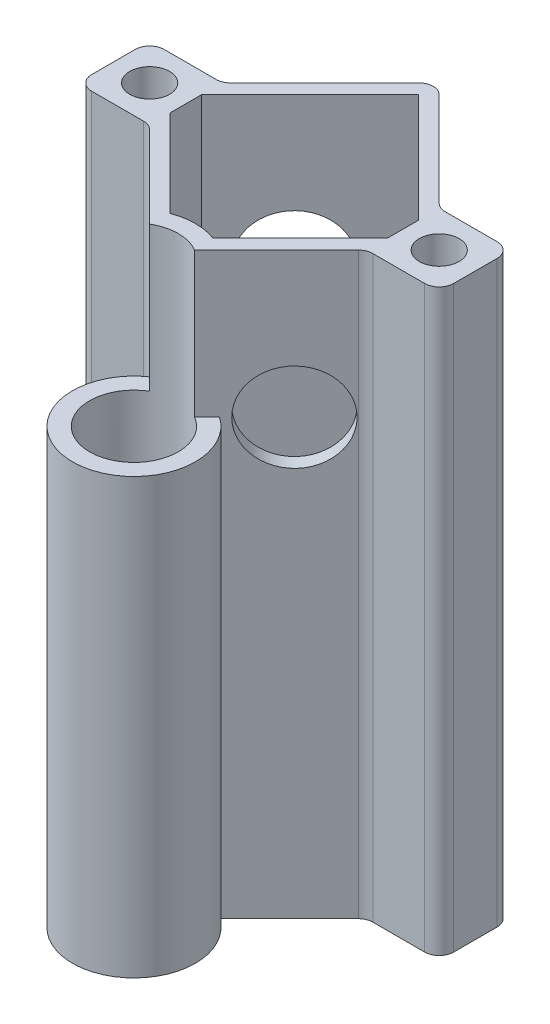
SolidWorks part; units mm, degrees
ref_plane "Front Plane" through (0, 0, 0) normal (0, 0, 1) x (1, 0, 0)
ref_plane "Top Plane" through (0, 0, 0) normal (0, 1, 0) x (1, 0, 0)
ref_plane "Right Plane" through (0, 0, 0) normal (1, 0, 0) x (0, 0, -1)
sketch "Sketch2" plane through (0, 0, 0) normal (0, 1, 0) x (1, 0, 0)
  line L32 (-25.4, 0) -> (-19.05, 0) construction
  line L33 (-25.4, 0) -> (0, 25.4)
  line L34 (-19.05, -6.35) -> (-31.75, -6.35)
  line L35 (-19.05, -6.35) -> (-19.05, 6.35)
  line L36 (-19.05, 6.35) -> (-31.75, 6.35)
  line L37 (-31.75, -6.35) -> (-31.75, 6.35)
  line L38 (-19.05, -6.35) -> (-31.75, 6.35) construction
  line L39 (-19.05, 6.35) -> (-31.75, -6.35) construction
  line L40 (19.05, -6.35) -> (31.75, -6.35)
  line L41 (19.05, -6.35) -> (19.05, 6.35)
  line L42 (19.05, 6.35) -> (31.75, 6.35)
  line L43 (31.75, -6.35) -> (31.75, 6.35)
  line L44 (19.05, -6.35) -> (31.75, 6.35) construction
  line L45 (19.05, 6.35) -> (31.75, -6.35) construction
  line L46 (0, -55) -> (0, 55) construction
  line L47 (0, 25.4) -> (25.4, 0)
  line L48 (25.4, 0) -> (0, -25.4)
  line L49 (0, -25.4) -> (-25.4, 0)
  line L50 (-19.05, 2.7579) -> (0, 21.8079)
  line L51 (19.05, 0) -> (25.4, 0) construction
  line L52 (0, 21.8079) -> (19.05, 2.7579)
  line L53 (19.05, -2.7579) -> (0, -21.8079)
  line L54 (0, -21.8079) -> (-19.05, -2.7579)
  line L55 (-21.8079, 0) -> (0, 21.8079) construction
  line L56 (0, -21.8079) -> (-21.8079, 0) construction
  line L57 (0, 21.8079) -> (21.8079, 0) construction
  line L58 (21.8079, 0) -> (0, -21.8079) construction
  circle A0 centre (25.4, 0) radius 3.4925
  circle A1 centre (-25.4, 0) radius 3.4925
  point P0 (0, 0)
  point P5 (0, 0)
  dimension "D1" = 50.8
  dimension "D2" = 6.35
  dimension "D4" = 6.985
  dimension "D3" = 2.54
  dimension "D5" = 50.8
  dimension "D6" = 12.7
extrude "Boss-Extrude1" add sketch "Sketch2" along normal blind 101.6 contours L42 L36 | L40 L34 | L50 L52 L41 L47 L33 L35 | A1 L49 L35 L33 | A1 L33 L36 L37 L34 L49 | L53 L54 L35 L49 L48 L41 | A0 L47 L41 L48 | A0 L48 L40 L43 L42 L47 region at (-20.5007, 0, 0) region at (-9.2116, 0, -15.5616) region at (-21.1172, 0, -4.5368) region at (20.5007, 0, 0) region at (25.4, 0, -6.1704) region at (-9.8384, 0, 12.5963)
fillet "Fillet1" radius 2.54 10 edges at (-31.75, 50.8, -6.35) (-31.75, 50.8, 6.35) (31.75, 50.8, 6.35) (31.75, 50.8, -6.35) (-19.05, 50.8, 6.35) (0, 50.8, 25.4) (19.05, 50.8, 6.35) (19.05, 50.8, -6.35) (0, 50.8, -25.4) (-19.05, 50.8, -6.35)
ref_axis "Axis2" through (0, -5.08, 0) along (0, 1, 0)
sketch "Sketch12" plane through (-12.7, 0, -12.7) normal (-0.7071, 0, -0.7071) x (-0.7071, 0, 0.7071)
  line L1 (7.9282, 101.6) -> (-15.4205, 101.6) construction
  line L2 (0, -5.08) -> (0, 106.68) construction
  circle A0 centre (0, 76.2) radius 7.7787
  dimension "D1" = 15.5575
  dimension "D2" = 25.4
extrude "Cut-Extrude2" cut sketch "Sketch12" against normal through all both and the other way through all
sketch "Sketch13" plane through (12.7, 0, -12.7) normal (0.7071, 0, -0.7071) x (-0.7071, 0, -0.7071)
  line L0 (0, -5.08) -> (0, 106.68) construction
  line L1 (15.4205, 101.6) -> (-7.9282, 101.6) construction
  circle A0 centre (0, 50.8) radius 7.7788
  dimension "D1" = 15.5575
  dimension "D2" = 50.8
extrude "Cut-Extrude3" cut sketch "Sketch13" against normal through all both and the other way through all
sketch "Sketch14" plane through (0, 0, 0) normal (0, -1, 0) x (1, 0, 0)
  line L0 (0, 28.1579) -> (0, 21.8079) construction
  circle A0 centre (0, 28.1579) radius 7.7788
  circle A1 centre (0, 28.1579) radius 10.795
  line M6 (-19.05, 2.7579) -> (0, 21.8079)
  line M7 (0, 21.8079) -> (19.05, 2.7579)
  line M9 (18.3061, 7.0939) -> (1.7961, 23.6039)
  arc M10 (1.7961, 23.6039) -> (-1.7961, 23.6039) centre (0, 21.8079) ccw
  line M11 (-1.7961, 23.6039) -> (-18.3061, 7.0939)
  dimension "D1" = 15.5575
  dimension "D2" = 21.59
  dimension "D3" = 6.35
extrude "Boss-Extrude2" add sketch "Sketch14" against normal blind 76.2
extrude "Cut-Extrude4" cut sketch "Sketch14<2>" against normal through all contours A0 M9 M11 M10 | L0 A0 M10 M7 M9 | L0 A0 M10 M11 M6 region at (1.5302, 0, 22.2739) region at (0, 0, 28.8626) region at (-1.5302, 0, 22.2739)
sketch "Sketch14<2>" plane through (0, 0, 0) normal (0, -1, 0) x (1, 0, 0) same geometry as "Sketch14"
sketch "Sketch15" plane through (0, 76.2, 0) normal (0, 1, 0) x (1, 0, 0)
  line L2 (1.3165, -20.4914) -> (3.7666, -18.0413)
  line L3 (-3.7666, -18.0413) -> (-1.3165, -20.4914)
  line L4 (1.3165, -20.4914) -> (3.7666, -18.0413)
  line L5 (-3.7666, -18.0413) -> (-1.3165, -20.4914)
  arc A2 (1.3165, -20.4914) -> (-1.3165, -20.4914) centre (0, -28.1579) ccw
  arc A3 (3.7666, -18.0413) -> (-3.7666, -18.0413) centre (0, -28.1579) ccw
  arc A4 (1.3165, -20.4914) -> (-1.3165, -20.4914) centre (0, -28.1579) ccw
  arc A5 (3.7666, -18.0413) -> (-3.7666, -18.0413) centre (0, -28.1579) ccw
  dimension "D1" = 0
extrude "Boss-Extrude3" add sketch "Sketch15" along normal up to surface (25.4 mm away) up to face at (0, 101.6, 0.5145)
